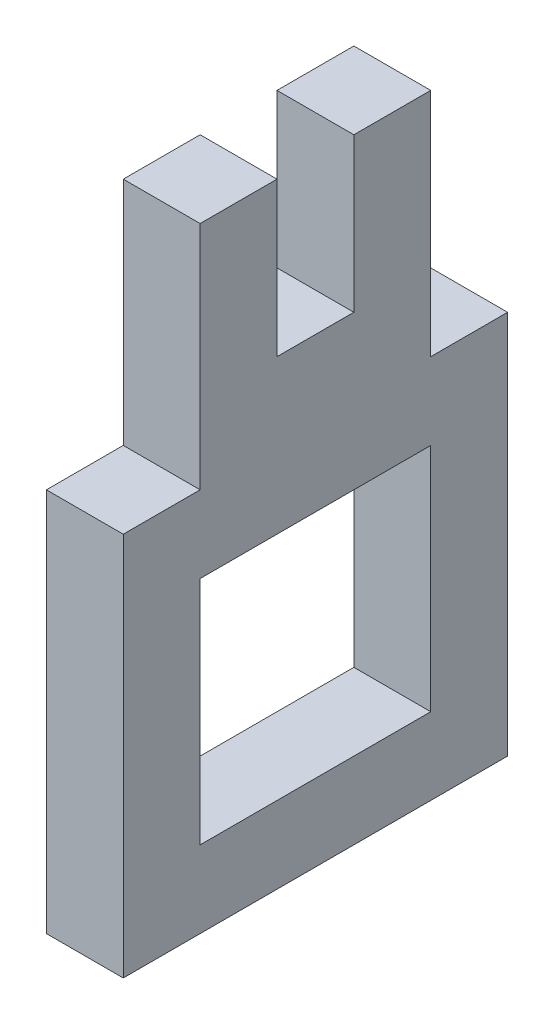
SolidWorks part; units mm, degrees
material "Pine"
ref_plane "Front Plane" through (0, 0, 0) normal (0, 0, 1) x (1, 0, 0)
ref_plane "Top Plane" through (0, 0, 0) normal (0, 1, 0) x (1, 0, 0)
ref_plane "Right Plane" through (0, 0, 0) normal (1, 0, 0) x (0, 0, -1)
sketch "Sketch2" plane through (0, 0, 0) normal (1, 0, 0) x (0, 0, -1)
  line L2 (12.7, 50.8) -> (12.7, 38.1)
  line L3 (12.7, 38.1) -> (19.05, 38.1)
  line L4 (19.05, 38.1) -> (19.05, 50.8)
  line L5 (19.05, 50.8) -> (25.4, 50.8)
  line L7 (31.75, 0) -> (0, 0)
  line L9 (6.35, 6.35) -> (25.4, 6.35)
  line L10 (6.35, 6.35) -> (6.35, 25.4)
  line L11 (6.35, 25.4) -> (25.4, 25.4)
  line L12 (25.4, 6.35) -> (25.4, 25.4)
  line L16 (25.4, 50.8) -> (25.4, 31.75)
  line L17 (25.4, 31.75) -> (31.75, 31.75)
  line L18 (31.75, 31.75) -> (31.75, 0)
  line L20 (6.35, 31.75) -> (0, 31.75)
  line L21 (0, 31.75) -> (0, 0)
  line L22 (12.7, 50.8) -> (6.35, 50.8)
  line L23 (6.35, 50.8) -> (6.35, 31.75)
  point P13 (15.875, 38.1)
  point P16 (15.875, 0)
  dimension "D1" = 6.35
  dimension "D2" = 19.05
  dimension "D3" = 19.05
  dimension "D4" = 6.35
  dimension "D7" = 12.7
  dimension "D5" = 6.35
  dimension "D6" = 6.35
  dimension "D8" = 6.35
  dimension "D9" = 6.35
  dimension "D10" = 6.35
  dimension "D11" = 25.4
extrude "Boss-Extrude1" add sketch "Sketch2" along normal blind 6.35
equation "\"D2@Sketch2\"=\"D3@Sketch2\""
